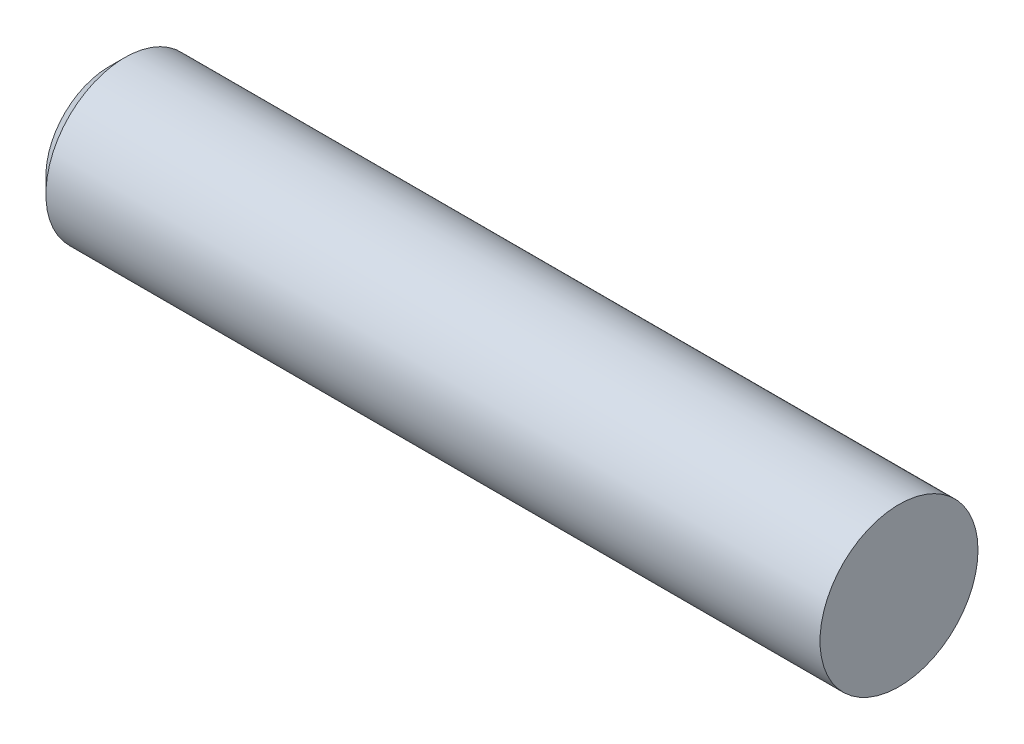
SolidWorks part; units mm, degrees
material "Alloy Steel"
ref_plane "Front" through (0, 0, 0) normal (0, 0, 1) x (1, 0, 0)
ref_plane "Top" through (0, 0, 0) normal (0, 1, 0) x (1, 0, 0)
ref_plane "Right" through (0, 0, 0) normal (1, 0, 0) x (0, 0, -1)
sketch "Sketch1" plane through (0, 0, 0) normal (0, 0, 1) x (1, 0, 0)
  line L0 (-7.9375, 0) -> (7.9375, 0) construction
  line L1 (7.9375, 1.5875) -> (7.9375, -1.5875) construction
  line L2 (-7.9375, 1.5875) -> (-7.9375, -1.5875) construction
  dimension "Length" = 15.875
  dimension "Diameter" = 3.175
sketch "Sketch2" plane through (0, 0, 0) normal (1, 0, 0) x (0, 0, -1)
  circle A0 centre (0, 0) radius 1.5875
extrude "Extrude1" add sketch "Sketch2" against normal up to vertex (7.9375 mm away) and the other way up to vertex (7.9375 mm away) up to point (-7.9375, 1.5875, 0) other way up to point (7.9375, 1.5875, 0)
chamfer "Chamfer1" distance 0.3175 angle 45 2 edges at (7.9375, 0, -1.5875) (-7.9375, 0, -1.5875)
other "DeleteFace1" face at (7.62, 0, -1.5875) and patch yes
ref_axis "Axis1" through (8.7312, 0, 0) along (-1, 0, 0)
equation "\"D1@Chamfer1\" = \"Diameter@Sketch1\"*.1"
